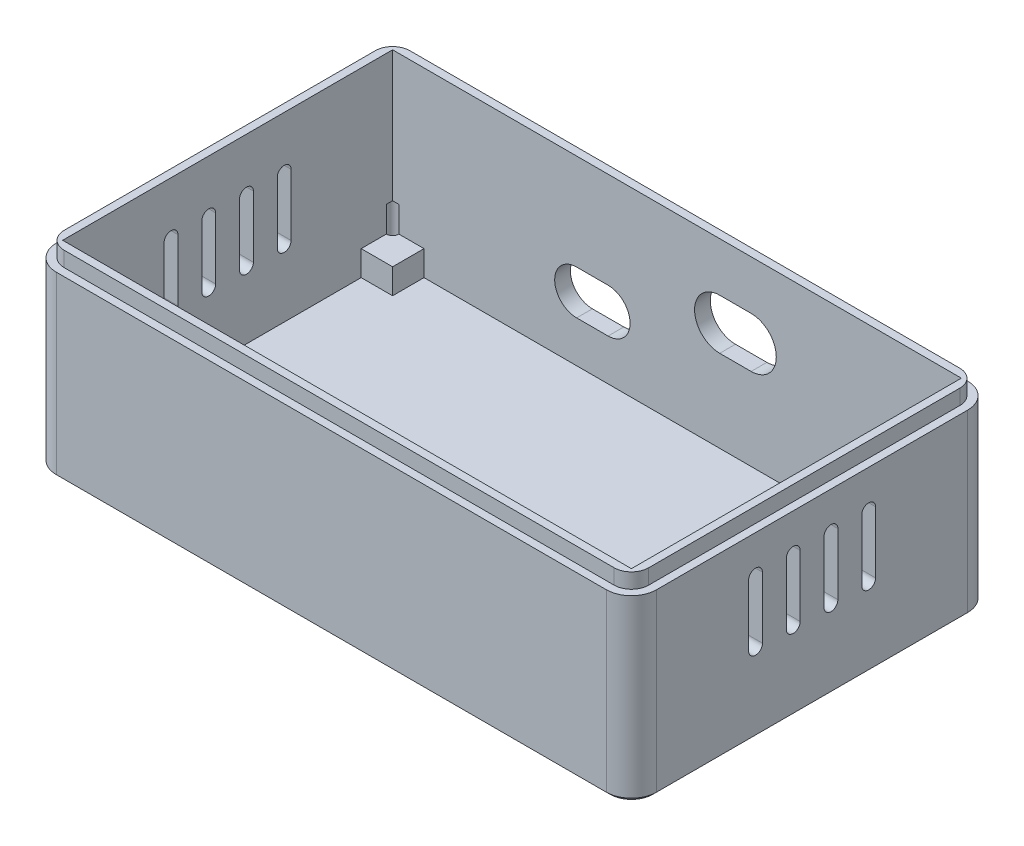
SolidWorks part; units mm, degrees
ref_plane "Front Plane" through (0, 0, 0) normal (0, 0, 1) x (1, 0, 0)
ref_plane "Top Plane" through (0, 0, 0) normal (0, 1, 0) x (1, 0, 0)
ref_plane "Right Plane" through (0, 0, 0) normal (1, 0, 0) x (0, 0, -1)
sketch "Croquis_contorno" plane through (0, 0, 0) normal (0, 1, 0) x (1, 0, 0)
  line L0 (-43.75, -28.75) -> (43.75, -28.75)
  line L1 (47.75, -24.75) -> (47.75, 24.75)
  line L2 (43.75, 28.75) -> (-43.75, 28.75)
  line L3 (-47.75, 24.75) -> (-47.75, -24.75)
  arc A0 (43.75, -28.75) -> (47.75, -24.75) centre (43.75, -24.75) ccw
  arc A1 (47.75, 24.75) -> (43.75, 28.75) centre (43.75, 24.75) ccw
  arc A2 (-43.75, 28.75) -> (-47.75, 24.75) centre (-43.75, 24.75) ccw
  arc A3 (-47.75, -24.75) -> (-43.75, -28.75) centre (-43.75, -24.75) ccw
  dimension "D3" = 4
  dimension "D1" = 95.5
  dimension "D2" = 57.5
extrude "Cuerpo" add sketch "Croquis_contorno" along normal blind 28.5
ref_plane "Plano_Top Plane_+28_5" through (0, 28.5, 0) normal (0, 1, 0) x (1, 0, 0)
sketch "Croquis_hueco_PCB" plane through (0, 28.5, 0) normal (0, 1, 0) x (1, 0, 0)
  line L1 (-45.25, -26.25) -> (45.25, -26.25)
  line L2 (-45.25, -26.25) -> (-45.25, 26.25)
  line L3 (-45.25, 26.25) -> (45.25, 26.25)
  line L4 (45.25, -26.25) -> (45.25, 26.25)
  line L5 (-45.25, -26.25) -> (45.25, 26.25) construction
  line L6 (-45.25, 26.25) -> (45.25, -26.25) construction
  dimension "D1" = 90.5
  dimension "D2" = 52.5
extrude "Hueco_PCB" cut sketch "Croquis_hueco_PCB" against normal blind 26.5
sketch "Croquis_labio" plane through (0, 28.5, 0) normal (0, 1, 0) x (1, 0, 0)
  line L0 (-43.75, -27.5) -> (43.75, -27.5)
  line L1 (46.5, -24.75) -> (46.5, 24.75)
  line L2 (43.75, 27.5) -> (-43.75, 27.5)
  line L3 (-46.5, 24.75) -> (-46.5, -24.75)
  line L5 (-45.25, -26.25) -> (45.25, -26.25)
  line L6 (-45.25, -26.25) -> (-45.25, 26.25)
  line L7 (-45.25, 26.25) -> (45.25, 26.25)
  line L8 (45.25, -26.25) -> (45.25, 26.25)
  line L9 (-45.25, -26.25) -> (45.25, 26.25) construction
  line L10 (-45.25, 26.25) -> (45.25, -26.25) construction
  arc A0 (43.75, -27.5) -> (46.5, -24.75) centre (43.75, -24.75) ccw
  arc A1 (46.5, 24.75) -> (43.75, 27.5) centre (43.75, 24.75) ccw
  arc A2 (-43.75, 27.5) -> (-46.5, 24.75) centre (-43.75, 24.75) ccw
  arc A3 (-46.5, -24.75) -> (-43.75, -27.5) centre (-43.75, -24.75) ccw
  point P12 (0, 0)
  dimension "D3" = 2.75
  dimension "D1" = 93
  dimension "D2" = 55
extrude "Labio_lip" add sketch "Croquis_labio" along normal blind 2.4
ref_plane "Plano_Top Plane_+2" through (0, 2, 0) normal (0, 1, 0) x (1, 0, 0)
sketch "Croquis_apoyos" plane through (0, 2, 0) normal (0, 1, 0) x (1, 0, 0)
  line L0 (45.25, 26.25) -> (-45.25, 26.25) construction
  line L1 (-45.25, -26.25) -> (-40.25, -26.25)
  line L2 (-45.25, -26.25) -> (-45.25, -21.25)
  line L3 (-45.25, -21.25) -> (-40.25, -21.25)
  line L4 (-40.25, -26.25) -> (-40.25, -21.25)
  line L5 (-45.25, -26.25) -> (-40.25, -21.25) construction
  line L6 (-45.25, -21.25) -> (-40.25, -26.25) construction
  line L7 (-45.25, 21.25) -> (-40.25, 21.25)
  line L8 (-45.25, 21.25) -> (-45.25, 26.25)
  line L9 (-45.25, 26.25) -> (-40.25, 26.25)
  line L10 (-40.25, 21.25) -> (-40.25, 26.25)
  line L11 (-45.25, 21.25) -> (-40.25, 26.25) construction
  line L12 (-45.25, 26.25) -> (-40.25, 21.25) construction
  line L13 (45.25, -26.25) -> (45.25, 26.25) construction
  line L14 (40.25, -26.25) -> (45.25, -26.25)
  line L15 (40.25, -26.25) -> (40.25, -21.25)
  line L16 (40.25, -21.25) -> (45.25, -21.25)
  line L17 (45.25, -26.25) -> (45.25, -21.25)
  line L18 (40.25, -26.25) -> (45.25, -21.25) construction
  line L19 (40.25, -21.25) -> (45.25, -26.25) construction
  line L21 (40.25, 21.25) -> (45.25, 21.25)
  line L22 (40.25, 21.25) -> (40.25, 26.25)
  line L23 (40.25, 26.25) -> (45.25, 26.25)
  line L24 (45.25, 21.25) -> (45.25, 26.25)
  line L25 (40.25, 21.25) -> (45.25, 26.25) construction
  line L26 (40.25, 26.25) -> (45.25, 21.25) construction
  point P0 (-42.75, 23.75)
  point P11 (42.75, -23.75)
  point P18 (42.75, 23.75)
  dimension "D1" = 5
  dimension "D2" = 5
extrude "Apoyos_PCB" add sketch "Croquis_apoyos" along normal blind 4
sketch "Croquis_alivios" plane through (0, 2, 0) normal (0, 1, 0) x (1, 0, 0)
  circle A0 centre (-45.25, -26.25) radius 1
  circle A1 centre (-45.25, 26.25) radius 1
  circle A2 centre (45.25, -26.25) radius 1
  circle A3 centre (45.25, 26.25) radius 1
  dimension "D1" = 2
extrude "Alivios_esquinas" cut sketch "Croquis_alivios" along normal blind 8.1
sketch "Croquis_salidas" plane through (0, 0, 0) normal (0, 0, 1) x (1, 0, 0)
  line L0 (6.8, 19.1) -> (11.8, 19.1) construction
  line L1 (6.8, 23.1) -> (11.8, 23.1)
  line L2 (6.8, 15.1) -> (11.8, 15.1)
  line L3 (-15.96, 12.1) -> (-10.96, 12.1) construction
  line L4 (-15.96, 15.6) -> (-10.96, 15.6)
  line L5 (-15.96, 8.6) -> (-10.96, 8.6)
  arc A0 (6.8, 23.1) -> (6.8, 15.1) centre (6.8, 19.1) ccw
  arc A1 (11.8, 15.1) -> (11.8, 23.1) centre (11.8, 19.1) ccw
  arc A2 (-15.96, 15.6) -> (-15.96, 8.6) centre (-15.96, 12.1) ccw
  arc A3 (-10.96, 8.6) -> (-10.96, 15.6) centre (-10.96, 12.1) ccw
  point P2 (9.3, 19.1)
  point P7 (-13.46, 12.1)
  point P14 (0, 0)
extrude "Salidas_USB_y_panel" cut sketch "Croquis_salidas" against normal through all
sketch "Croquis_ventilas" plane through (0, 0, 0) normal (1, 0, 0) x (0, 0, -1)
  line L0 (-9, 12.7) -> (-9, 22.5) construction
  line L1 (-10.1, 12.7) -> (-10.1, 22.5)
  line L2 (-7.9, 12.7) -> (-7.9, 22.5)
  line L3 (-3, 12.7) -> (-3, 22.5) construction
  line L4 (-4.1, 12.7) -> (-4.1, 22.5)
  line L5 (-1.9, 12.7) -> (-1.9, 22.5)
  line L6 (3, 12.7) -> (3, 22.5) construction
  line L7 (1.9, 12.7) -> (1.9, 22.5)
  line L8 (4.1, 12.7) -> (4.1, 22.5)
  line L9 (9, 12.7) -> (9, 22.5) construction
  line L10 (7.9, 12.7) -> (7.9, 22.5)
  line L11 (10.1, 12.7) -> (10.1, 22.5)
  arc A0 (-10.1, 12.7) -> (-7.9, 12.7) centre (-9, 12.7) ccw
  arc A1 (-7.9, 22.5) -> (-10.1, 22.5) centre (-9, 22.5) ccw
  arc A2 (-4.1, 12.7) -> (-1.9, 12.7) centre (-3, 12.7) ccw
  arc A3 (-1.9, 22.5) -> (-4.1, 22.5) centre (-3, 22.5) ccw
  arc A4 (1.9, 12.7) -> (4.1, 12.7) centre (3, 12.7) ccw
  arc A5 (4.1, 22.5) -> (1.9, 22.5) centre (3, 22.5) ccw
  arc A6 (7.9, 12.7) -> (10.1, 12.7) centre (9, 12.7) ccw
  arc A7 (10.1, 22.5) -> (7.9, 22.5) centre (9, 22.5) ccw
  point P2 (-9, 17.6)
  point P7 (-3, 17.6)
  point P14 (3, 17.6)
  point P21 (9, 17.6)
  point P28 (0, 0)
extrude "Ventilas_laterales" cut sketch "Croquis_ventilas" along normal through all and the other way through all
chamfer "Chaflan_base" distance 0.6 angle 45 8 edges at (0, 0, 28.75) (46.5784, 0, 27.5784) (47.75, 0, 0) (46.5784, 0, -27.5784) (0, 0, -28.75) (-46.5784, 0, -27.5784) (-47.75, 0, 0) (-46.5784, 0, 27.5784) tangent propagation no
